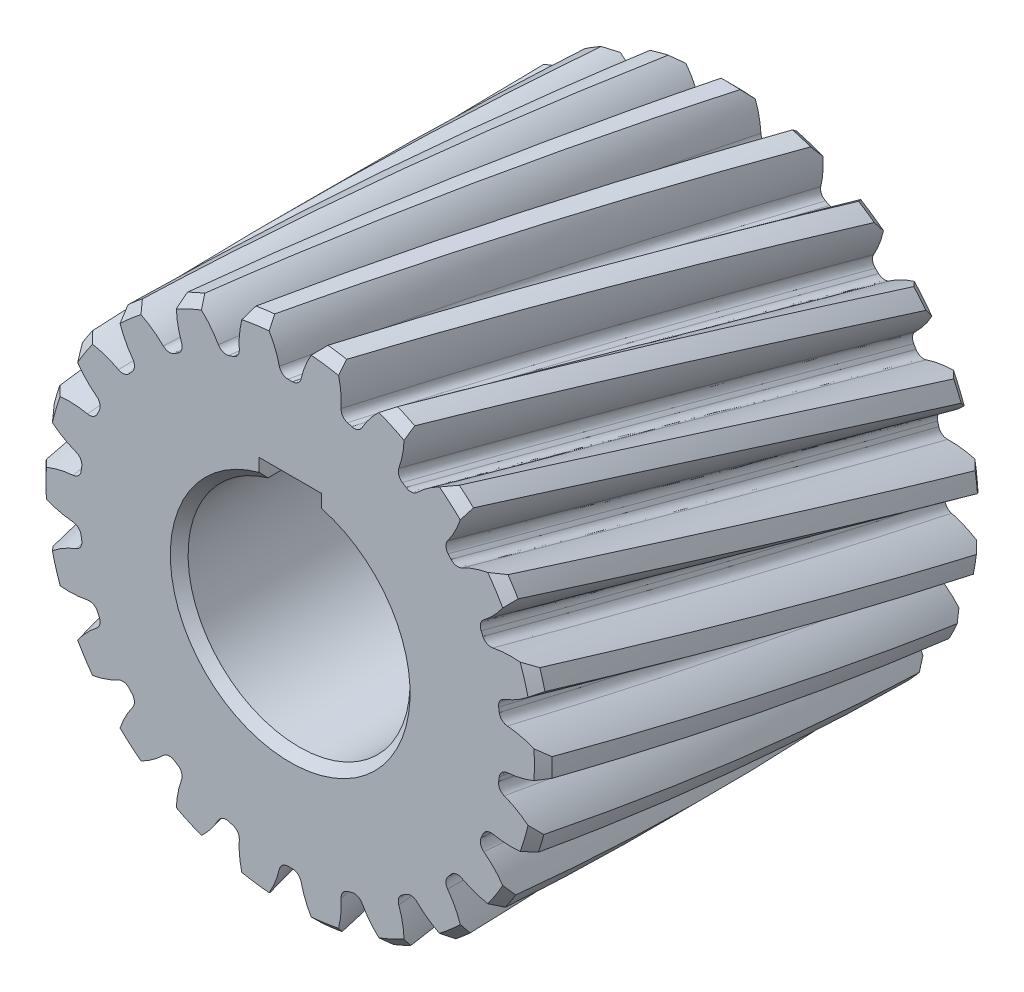
SolidWorks part; units mm, degrees
material "Gray Cast Iron (SN)"
ref_plane "Front Plane" through (0, 0, 0) normal (0, 0, 1) x (1, 0, 0)
ref_plane "Top Plane" through (0, 0, 0) normal (0, 1, 0) x (1, 0, 0)
ref_plane "Right Plane" through (0, 0, 0) normal (1, 0, 0) x (0, 0, -1)
sketch "Sketch1" plane through (0, 0, 0) normal (0, 0, 1) x (1, 0, 0)
  line L2 (7, 24) -> (7, 29)
  line L3 (7, 29) -> (-7, 29)
  line L4 (-7, 24) -> (-7, 29)
  circle A0 centre (0, 0) radius 57
  arc A1 (-7, 24) -> (7, 24) centre (0, 0) ccw
  point P4 (0, 25)
  dimension "D1" = 50
  dimension "D2" = 114
  dimension "D4" = 14
extrude "Boss-Extrude1" add sketch "Sketch1" against normal blind 100
chamfer "Chamfer1" distance 2 angle 45 4 edges at (0, -25, -100) (57, 0, -100) (57, 0, 0) (0, -25, 0)
sketch "Sketch3" plane through (0, 0, 0) normal (0, 0, 1) x (1, 0, 0)
  circle A0 centre (0, 0) radius 57
  dimension "D1" = 114
curve "Helix/Spiral1" pitch 1371 height 100 turns 0.0729
sketch "Sketch4" plane through (0, 0, 0) normal (0, 0, 1) x (1, 0, 0)
  line L0 (0, 0) -> (0, 74.4238) construction
  line L1 (-0.5, 47.5) -> (0.5, 47.5)
  arc A0 (6, 56.6833) -> (-6, 56.6833) centre (0, 0) ccw
  circle A1 centre (0, 0) radius 57 construction
  arc A2 (-6, 56.6833) -> (-2.4502, 49.0563) centre (-21.9518, 44.6193) cw
  arc A3 (6, 56.6833) -> (2.4502, 49.0563) centre (21.9518, 44.6193) ccw
  arc A4 (-2.4502, 49.0563) -> (-0.5, 47.5) centre (-0.5, 49.5) ccw
  arc A5 (2.4502, 49.0563) -> (0.5, 47.5) centre (0.5, 49.5) cw
  point P14 (0, 47.5)
  point P17 (0, 57)
  dimension "D1" = 2
  dimension "D2" = 20
  dimension "D3" = 0.5
  dimension "D4" = 9.5
  dimension "D5" = 12
sweep "Cut-Sweep1" cut profiles "Sketch4" path "Helix/Spiral1" align with end faces yes
pattern_circular "CirPattern1" count 22 over 360 about axis through (0, 0, -100) along (0, 0, 1) of "Cut-Sweep1" reverse direction yes
